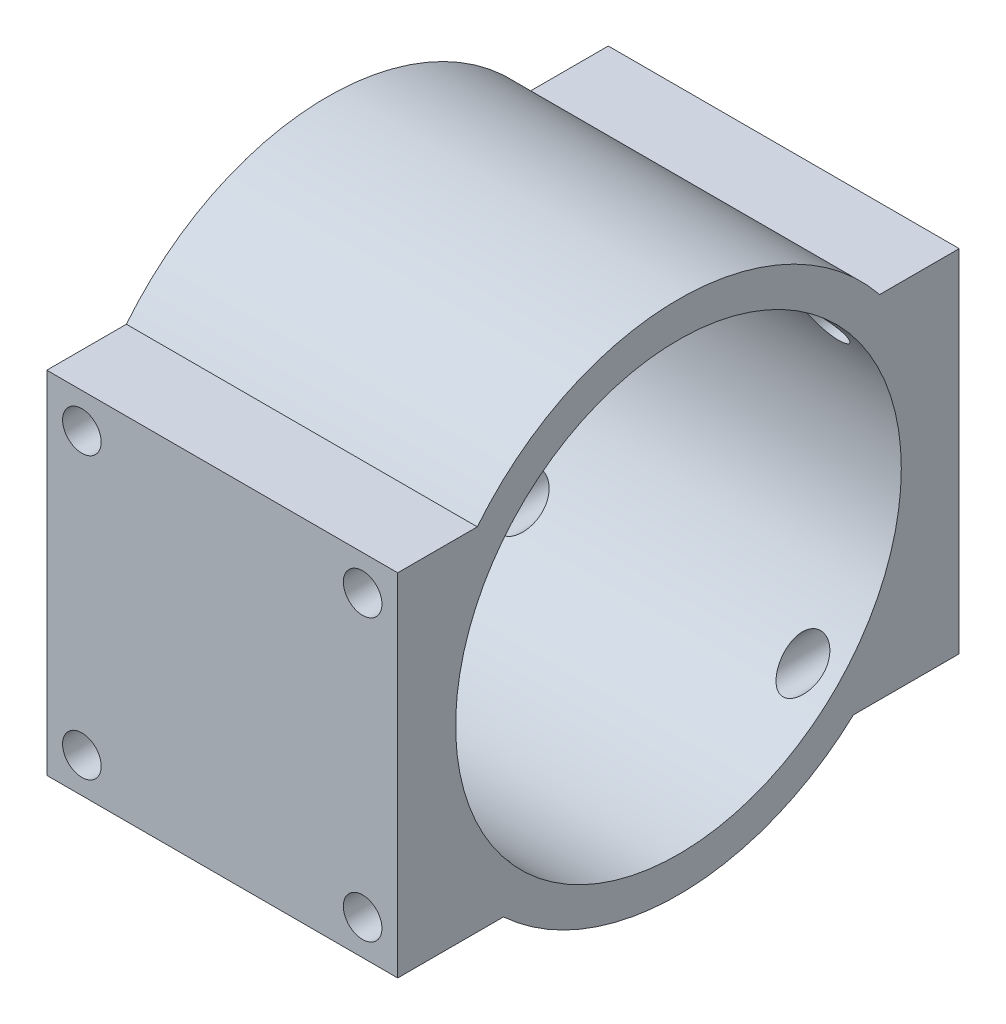
SolidWorks part; units mm, degrees
ref_plane "Front Plane" through (0, 0, 0) normal (0, 0, 1) x (1, 0, 0)
ref_plane "Top Plane" through (0, 0, 0) normal (0, 1, 0) x (1, 0, 0)
ref_plane "Right Plane" through (0, 0, 0) normal (1, 0, 0) x (0, 0, -1)
sketch "Sketch1" plane through (0, 0, 0) normal (0, 0, 1) x (1, 0, 0)
  line L1 (-25, 23) -> (25, 23)
  line L2 (-25, 23) -> (-25, -27)
  line L3 (-25, -27) -> (25, -27)
  line L4 (25, 23) -> (25, -27)
  line L5 (-25, 23) -> (25, -27) construction
  line L6 (-25, -27) -> (25, 23) construction
  circle A1 centre (-20, 18) radius 2.75
  circle A2 centre (20, 18) radius 2.75
  circle A3 centre (20, -22) radius 2.75
  circle A4 centre (-20, -22) radius 2.75
  point P0 (0, -2)
  dimension "D6" = 5.5
  dimension "D1" = 2
  dimension "D2" = 50
  dimension "D3" = 50
  dimension "D5" = 20
  dimension "D7" = 20
  dimension "D9" = 20
  dimension "D10" = 20
extrude "Boss-Extrude1" add sketch "Sketch1" along normal blind 40
sketch "Sketch2" plane through (0, 0, 0) normal (1, 0, 0) x (0, 0, -1)
  circle A0 centre (0, 0) radius 31.75
  dimension "D1" = 63.5
extrude "Cut-Extrude1" cut sketch "Sketch2" against normal through all and the other way through all
sketch "Sketch3" plane through (25, 0, 0) normal (1, 0, 0) x (0, 0, -1)
  arc A0 (-21.8875, 23) -> (-16.7052, -27) centre (0, 0) ccw construction
  arc A1 (-21.8875, 23) -> (-16.7052, -27) centre (0, 0) ccw
  arc A2 (-21.8875, 23) -> (-16.7052, -27) centre (0, 0) cw
  arc A3 (-25.3343, 26.622) -> (-19.3359, -31.252) centre (0, 0) cw
  arc A4 (-25.3343, 26.622) -> (-19.3359, -31.252) centre (0, 0) ccw
  arc M2 (-16.7052, -27) -> (-21.8875, 23) centre (0, 0) cw
  dimension "D1" = 5
extrude "Boss-Extrude2" add sketch "Sketch3" against normal blind 50
extrude "Cut-Extrude2" cut sketch "Sketch1<2>" against normal through all and the other way blind 50 contours A1 | A4 | A3 | A2 region at (-20, 18, 0)
sketch "Sketch1<2>" plane through (0, 0, 0) normal (0, 0, 1) x (1, 0, 0) same geometry as "Sketch1"
extrude "Boss-Extrude3" add sketch "Sketch1<3>" against normal blind 40
sketch "Sketch1<3>" plane through (0, 0, 0) normal (0, 0, 1) x (1, 0, 0) same geometry as "Sketch1"
extrude "Cut-Extrude3" cut sketch "Sketch3<2>" against normal through all contours A2 M2 region at (25, 0, 0)
sketch "Sketch3<2>" plane through (25, 0, 0) normal (1, 0, 0) x (0, 0, -1) same geometry as "Sketch3"
scale "Scale1" scale about centroid uniform scaling yes scale factor 1.015
